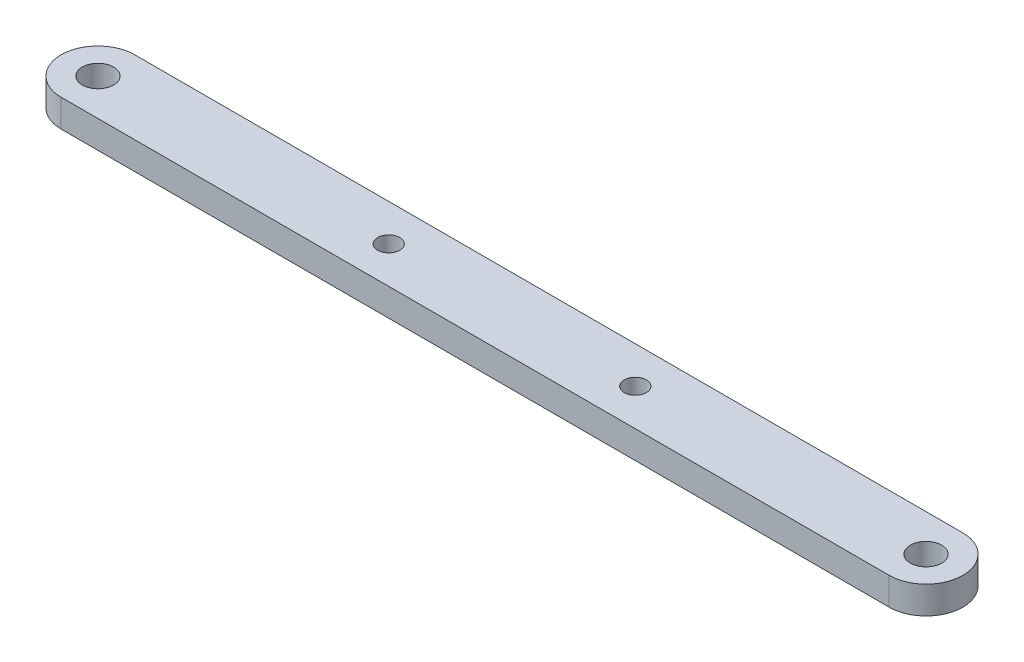
SolidWorks part; units mm, degrees
ref_plane "Front Plane" through (0, 0, 0) normal (0, 0, 1) x (1, 0, 0)
ref_plane "Top Plane" through (0, 0, 0) normal (0, 1, 0) x (1, 0, 0)
ref_plane "Right Plane" through (0, 0, 0) normal (1, 0, 0) x (0, 0, -1)
sketch "Sketch1" plane through (0, 0, 0) normal (0, 1, 0) x (1, 0, 0)
  line L0 (0, 0) -> (90, 0) construction
  line L1 (0, 4) -> (90, 4)
  line L2 (0, -4) -> (90, -4)
  arc A0 (0, 4) -> (0, -4) centre (0, 0) ccw
  arc A1 (90, -4) -> (90, 4) centre (90, 0) ccw
  point P3 (45, 0)
  dimension "D1" = 90
  dimension "D2" = 8
extrude "Boss-Extrude1" add sketch "Sketch1" along normal blind 3
hole_wizard "M3 Clearance Hole1" positions "Sketch3" profile "Sketch4" hole size "M3" standard "ANSI Metric" end condition through all
sketch "Sketch3" plane through (0, 3, 0) normal (0, 1, 0) x (1, 0, 0)
  point P0 (90, 0)
  point P3 (0, 0)
sketch "Sketch4" plane through (90, 3, 0) normal (1, 0, 0) x (0, 0, 1)
  line L0 (0, 0) -> (0, 3)
  line L1 (0, 3) -> (1.7, 3)
  line L2 (1.7, 3) -> (1.7, 0)
  line L5 (1.7, 0) -> (0, 0)
  line L11 (0, -6.35) -> (0, 107.95) construction
  dimension "Thru Hole Dia." = 3.4
  dimension "Thru Hole Depth" = 3
hole_wizard "M2 Clearance Hole1" positions "Sketch6" profile "Sketch5" hole size "M2" standard "ANSI Metric" end condition through all
sketch "Sketch6" plane through (0, 3, 0) normal (0, 1, 0) x (1, 0, 0)
  line L3 (-4, 0) -> (94, 0) construction
  line L8 (31.6, 0) -> (45, 0) construction
  line L9 (45, 0) -> (58.4, 0) construction
  arc A0 (0, 4) -> (0, -4) centre (0, 0) ccw construction
  arc A1 (90, -4) -> (90, 4) centre (90, 0) ccw construction
  point P0 (58.4, 0)
  point P2 (31.6, 0)
  dimension "D1" = 13.4
  dimension "D2" = 13.4
sketch "Sketch5" plane through (58.4, 3, 0) normal (1, 0, 0) x (0, 0, 1)
  line L0 (0, 0) -> (0, 3)
  line L1 (0, 3) -> (1.2, 3)
  line L2 (1.2, 3) -> (1.2, 0)
  line L5 (1.2, 0) -> (0, 0)
  line L11 (0, -6.35) -> (0, 107.95) construction
  dimension "Thru Hole Dia." = 2.4
  dimension "Thru Hole Depth" = 3
